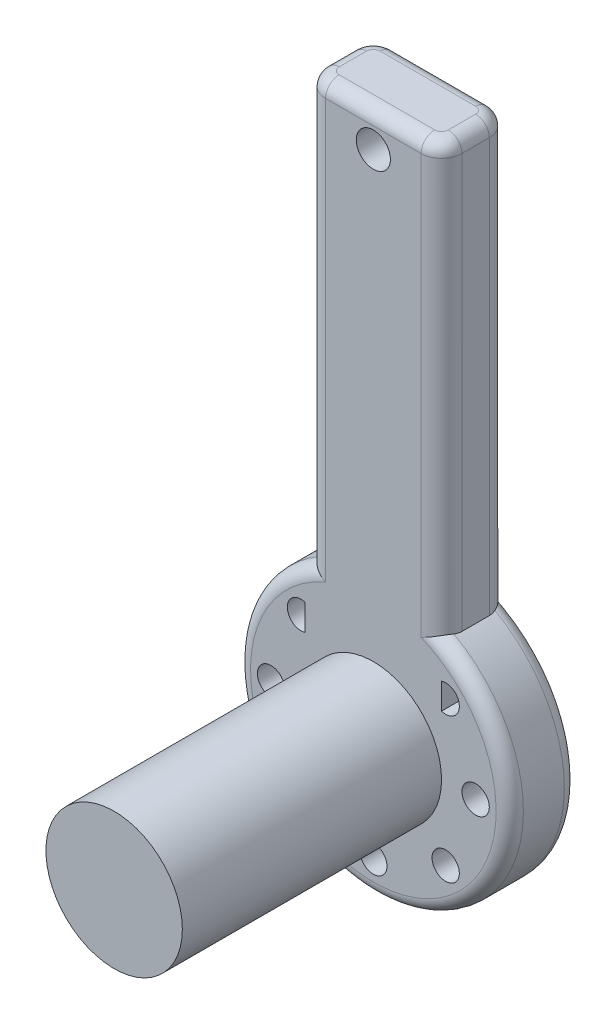
SolidWorks part; units mm, degrees
ref_plane "前视基准面" through (0, 0, 0) normal (0, 0, 1) x (1, 0, 0)
ref_plane "上视基准面" through (0, 0, 0) normal (0, 1, 0) x (1, 0, 0)
ref_plane "右视基准面" through (0, 0, 0) normal (1, 0, 0) x (0, 0, -1)
other "Configuration Table"
sketch "草图1" plane through (0, 0, 0) normal (0, 0, 1) x (1, 0, 0)
  circle A0 centre (0, 0) radius 10
  dimension "D1" = 20
extrude "凸台-拉伸2" add sketch "草图1" along normal blind 38
sketch "草图2" plane through (0, 0, 0) normal (0, 0, 1) x (1, 0, 0)
  circle A0 centre (0, 0) radius 20
  dimension "D1" = 40
extrude "凸台-拉伸3" add sketch "草图2" against normal blind 10
sketch "草图4" plane through (0, 0, 0) normal (0, 0, 1) x (1, 0, 0)
  circle A0 centre (0, 0) radius 15 construction
  circle A1 centre (-15, 0) radius 2
  circle A2 centre (0.0003, 0.0007) radius 15 construction
  circle A3 centre (-10.6063, 10.6073) radius 2
  circle A4 centre (0.001, 0.001) radius 15 construction
  circle A5 centre (0.001, 15.001) radius 2
  circle A6 centre (0.0017, 0.0007) radius 15 construction
  circle A7 centre (10.6083, 10.6073) radius 2
  circle A8 centre (0.002, 0) radius 15 construction
  circle A9 centre (15.002, 0) radius 2
  circle A10 centre (0.0017, -0.0007) radius 15 construction
  circle A11 centre (10.6083, -10.6073) radius 2
  circle A12 centre (0.001, -0.001) radius 15 construction
  circle A13 centre (0.001, -15.001) radius 2
  circle A14 centre (0.0003, -0.0007) radius 15 construction
  circle A15 centre (-10.6063, -10.6073) radius 2
  point P36 (0.001, 0)
  dimension "D1" = 30
  dimension "D2" = 4
  dimension "D3" = 8
extrude "切除-拉伸1" cut sketch "草图4" against normal mid plane 90
sketch "草图6" plane through (0, 0, 0) normal (0, 1, 0) x (1, 0, 0)
  line L0 (-10, 0) -> (10, 0)
  line L1 (-10, 10) -> (10, 10)
  line L2 (-8.6063, 10) -> (-12.6063, 10) construction
  line L4 (10, 0) -> (10, 10)
  line L5 (12.6083, 10) -> (8.6083, 10) construction
  line L7 (-20, 0) -> (20, 0) construction
  line L8 (-10, 0) -> (-10, 10)
extrude "凸台-拉伸4" add sketch "草图6" along normal blind 80
sketch "草图8" plane through (0, 0, 0) normal (0, 0, 1) x (1, 0, 0)
  line L0 (-10, 80) -> (10, 80) construction
  circle A0 centre (0, 75) radius 2.5
  dimension "D1" = 5
  dimension "D2" = 5
extrude "切除-拉伸3" cut sketch "草图8" against normal mid plane 80
fillet "圆角2" radius 3 4 edges at (-10, 48.6603, 0) (10, 48.6603, 0) (10, 48.6603, -10) (-10, 48.6603, -10)
fillet "圆角3" radius 2 8 edges at (0, 80, 0) (-10, 80, -5) (10, 80, -5) (0, 80, -10) (-9.1213, 80, -9.1213) (9.1213, 80, -9.1213) (9.1213, 80, -0.8787) (-9.1213, 80, -0.8787)
fillet "圆角4" radius 2 2 edges at (-8.9872, 17.867, -0.7526) (0, -20, 0)
fillet "圆角5" radius 2 2 edges at (8.9872, 17.867, -9.2474) (0, -20, -10)
